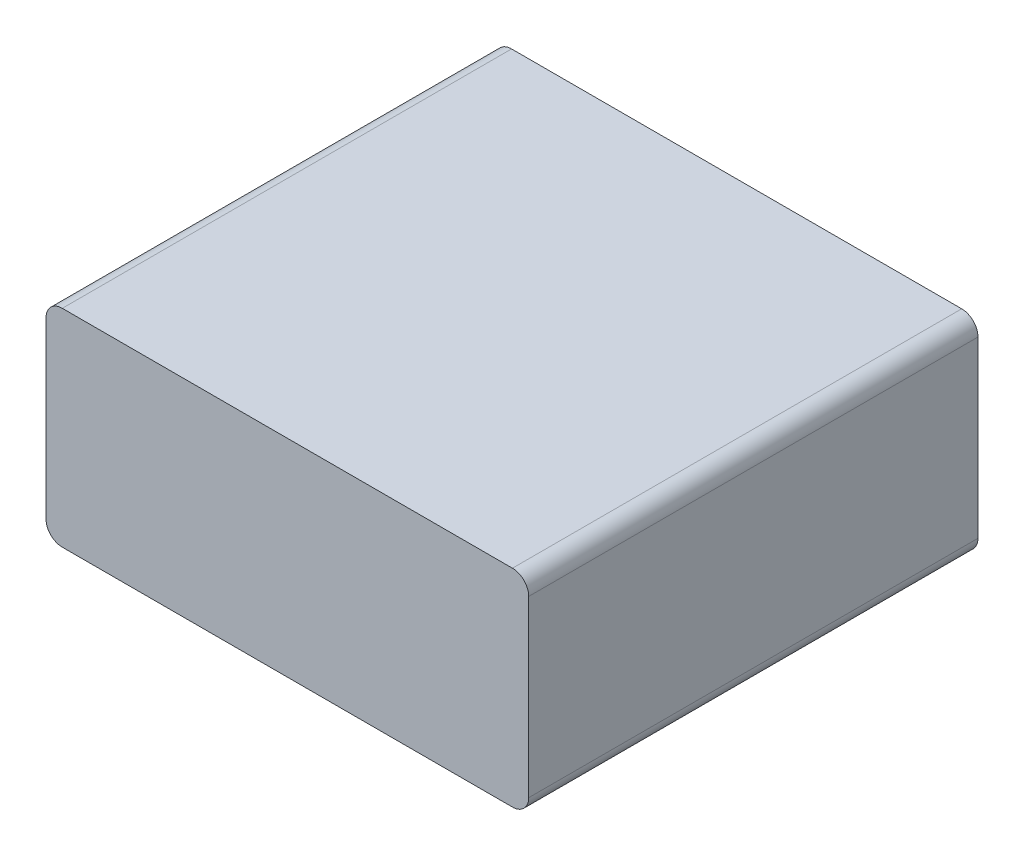
SolidWorks part; units mm, degrees
material "Pine"
ref_plane "Front Plane" through (0, 0, 0) normal (0, 0, 1) x (1, 0, 0)
ref_plane "Top Plane" through (0, 0, 0) normal (0, 1, 0) x (1, 0, 0)
ref_plane "Right Plane" through (0, 0, 0) normal (1, 0, 0) x (0, 0, -1)
sketch "Sketch1" plane through (0, 0, 0) normal (0, 0, 1) x (1, 0, 0)
  line L1 (41.45, -19.05) -> (-41.45, -19.05)
  line L2 (44.45, -16.05) -> (44.45, 16.05)
  line L3 (41.45, 19.05) -> (-41.45, 19.05)
  line L4 (-44.45, -16.05) -> (-44.45, 16.05)
  line L5 (44.45, -19.05) -> (-44.45, 19.05) construction
  line L6 (44.45, 19.05) -> (-44.45, -19.05) construction
  arc A0 (-41.45, -19.05) -> (-44.45, -16.05) centre (-41.45, -16.05) cw
  arc A1 (-41.45, 19.05) -> (-44.45, 16.05) centre (-41.45, 16.05) ccw
  arc A2 (44.45, 16.05) -> (41.45, 19.05) centre (41.45, 16.05) ccw
  arc A3 (41.45, -19.05) -> (44.45, -16.05) centre (41.45, -16.05) ccw
  point P0 (0, 0)
  dimension "D3" = 3
  dimension "D1" = 88.9
  dimension "D2" = 38.1
extrude "Boss-Extrude1" add sketch "Sketch1" along normal blind 82.74
equation "\"ChainSeperation\"= 80"
